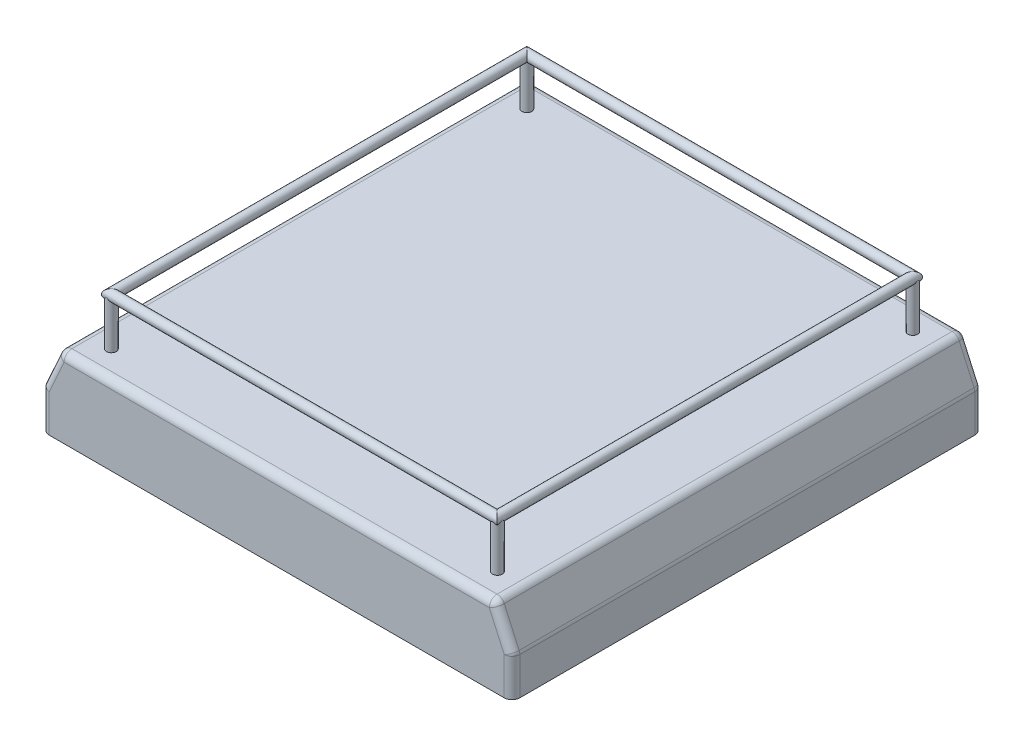
SolidWorks part; units mm, degrees
ref_plane "Front Plane" through (0, 0, 0) normal (0, 0, 1) x (1, 0, 0)
ref_plane "Top Plane" through (0, 0, 0) normal (0, 1, 0) x (1, 0, 0)
ref_plane "Right Plane" through (0, 0, 0) normal (1, 0, 0) x (0, 0, -1)
sketch "Sketch2" plane through (0, 0, 0) normal (0, 0, 1) x (1, 0, 0)
  line L0 (-600, 72) -> (-600, 172)
  line L1 (-600, 172) -> (-555, 272)
  line L2 (-555, 272) -> (0, 272)
  line L3 (-580, 72) -> (-580, 167.7073)
  line L4 (-580, 167.7073) -> (-542.0683, 252)
  line L5 (-542.0683, 252) -> (0, 252)
  line L6 (-600, 72) -> (-580, 72)
  line L7 (0, 0) -> (0, 500.2989) construction
  line L8 (542.0683, 252) -> (0, 252)
  line L9 (555, 272) -> (0, 272)
  line L10 (600, 72) -> (580, 72)
  line L11 (580, 167.7073) -> (542.0683, 252)
  line L12 (580, 72) -> (580, 167.7073)
  line L13 (600, 172) -> (555, 272)
  line L14 (600, 72) -> (600, 172)
  dimension "D1" = 100
  dimension "D2" = 45
  dimension "D3" = 200
  dimension "D4" = 600
  dimension "D5" = 20
extrude "Boss-Extrude1" add sketch "Sketch2" along normal blind 1160 from offset 20
sketch "Sketch3" plane through (0, 0, 1180) normal (0, 0, 1) x (1, 0, 0)
  line L0 (600, 72) -> (600, 172) construction
  line L5 (-600, 172) -> (-600, 72) construction
  line L6 (-555, 272) -> (-600, 172) construction
  line L7 (555, 272) -> (-555, 272) construction
  line L8 (600, 172) -> (555, 272) construction
  line L13 (600, 72) -> (600, 172)
  line L14 (600, 172) -> (555, 272)
  line L15 (555, 272) -> (-555, 272)
  line L16 (-555, 272) -> (-600, 172)
  line L17 (-600, 172) -> (-600, 72)
  line L18 (-600, 72) -> (600, 72)
extrude "Boss-Extrude2" add sketch "Sketch3" along normal blind 20
sketch "Sketch4" plane through (0, 0, 20) normal (0, 0, -1) x (-1, 0, 0)
  line L0 (600, 172) -> (600, 72) construction
  line L1 (555, 272) -> (600, 172) construction
  line L2 (-555, 272) -> (555, 272) construction
  line L3 (-600, 172) -> (-555, 272) construction
  line L4 (-600, 72) -> (-600, 172) construction
  line L5 (600, 172) -> (600, 72)
  line L6 (555, 272) -> (600, 172)
  line L7 (-555, 272) -> (555, 272)
  line L8 (-600, 172) -> (-555, 272)
  line L9 (-600, 72) -> (-600, 172)
  line L10 (-600, 72) -> (600, 72)
extrude "Boss-Extrude3" add sketch "Sketch4" along normal blind 20
fillet "Fillet3" radius 20 5 edges at (-600, 122, 0) (-577.5, 222, 0) (0, 272, 0) (600, 122, 0) (577.5, 222, 0)
fillet "Fillet4" radius 20 12 edges at (594.1421, 170.7427, 5.8579) (551.2124, 266.1421, 5.8579) (-551.2124, 266.1421, 5.8579) (600, 172, 610) (555, 272, 610) (600, 122, 1200) (577.5, 222, 1200) (-600, 122, 1200) (-577.5, 222, 1200) (0, 272, 1200) (-580, 167.7073, 600) (-555, 272, 610)
ref_plane "Plane1" through (0, 392, 0) normal (0, 1, 0) x (1, 0, 0)
sketch "Sketch6" plane through (0, 392, 0) normal (0, 1, 0) x (1, 0, 0)
  line L0 (492.0683, -1130) -> (-492.0683, -1130)
  line L1 (-492.0683, -1130) -> (-492.0683, -70)
  line L2 (-492.0683, -70) -> (492.0683, -70)
  line L3 (492.0683, -70) -> (492.0683, -1130)
  line L4 (-542.0683, -1180) -> (542.0683, -1180) construction
  line L5 (542.0683, -1180) -> (542.0683, -20) construction
  line L6 (542.0683, -20) -> (-542.0683, -20) construction
  line L7 (-542.0683, -20) -> (-542.0683, -1180) construction
  dimension "D1" = 50
  dimension "D2" = 50
  dimension "D3" = 50
  dimension "D4" = 50
sketch3d "3DSketch1"
  line L0 (491.9682, 392, 70) -> (491.9682, 272.1089, 70)
  line L1 (-492.0683, 392, 70) -> (492.0683, 392, 70) construction
  line L2 (492.0683, 392, 1129.3394) -> (492.0683, 267.4453, 1129.3394)
  line L5 (-492.0683, 392, 70) -> (-492.0683, 269.9889, 70)
  line L6 (492.0683, 392, 70) -> (492.0683, 392, 1130) construction
  line L8 (-491.5718, 392, 1130) -> (-491.5718, 253.5155, 1130)
  line L9 (492.0683, 392, 1130) -> (-492.0683, 392, 1130) construction
  point P14 (-491.5718, 253.5155, 1130)
other "Round end 25 X 2.4(1)" corner treatment miter
ref_plane "Plane2" through (492.0683, 392, 1130) normal (-1, 0, 0) x (0, 0, 1)
sketch "Sketch1" plane through (492.0683, 392, 1130) normal (-1, 0, 0) x (0, 0, 1)
  circle A0 centre (0, 0) radius 10.1
  circle A1 centre (0, 0) radius 12.5
  point P3 (0, 0)
  dimension "Out_dia" = 25
  dimension "D1" = 2.4
other "Round end 25 X 2.4(2)" corner treatment miter
ref_plane "Plane3" through (491.9682, 392, 70) normal (0, -1, 0) x (1, 0, 0)
sketch "Sketch11" plane through (491.9682, 392, 70) normal (0, -1, 0) x (1, 0, 0)
  circle A0 centre (0, 0) radius 10.1
  circle A1 centre (0, 0) radius 12.5
  point P3 (0, 0)
  dimension "Out_dia" = 25
  dimension "D1" = 2.4
sketch "Sketch12" plane through (-600, 0, 0) normal (-1, 0, 0) x (0, 0, 1)
  line L1 (550, 157.7189) -> (650, 157.7189)
  line L2 (550, 157.7189) -> (550, 87.7189)
  line L3 (550, 87.7189) -> (650, 87.7189)
  line L4 (650, 157.7189) -> (650, 87.7189)
  line L6 (20, 172) -> (20, 72) construction
  point P4 (600, 87.7189)
  dimension "D1" = 580
  dimension "D2" = 100
  dimension "D3" = 70
extrude "Cut-Extrude1" cut sketch "Sketch12" against normal blind 10
